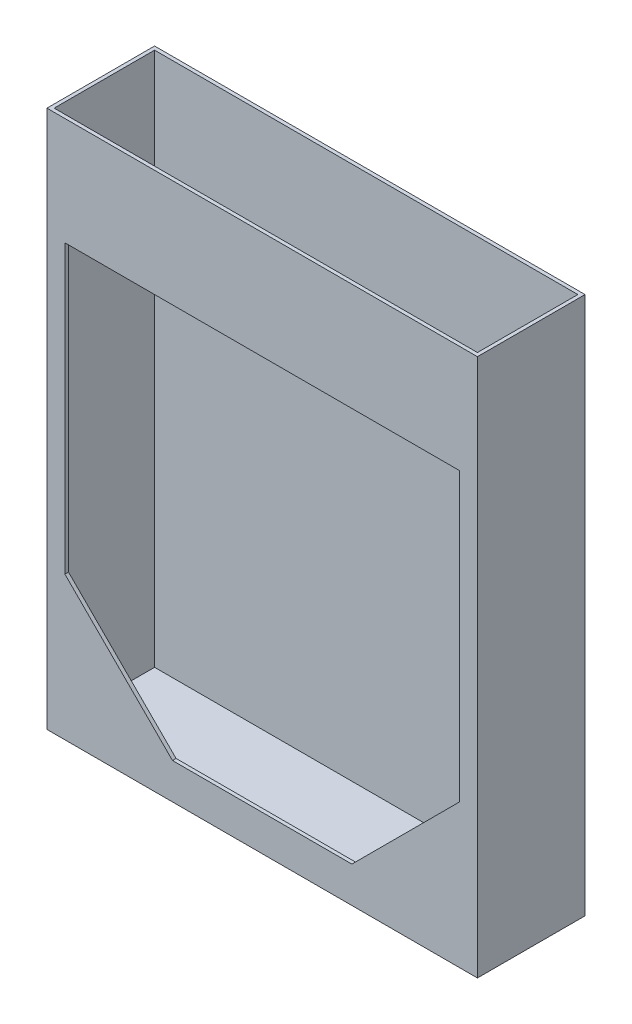
SolidWorks part; units mm, degrees
ref_plane "Front Plane" through (0, 0, 0) normal (0, 0, 1) x (1, 0, 0)
ref_plane "Top Plane" through (0, 0, 0) normal (0, 1, 0) x (1, 0, 0)
ref_plane "Right Plane" through (0, 0, 0) normal (1, 0, 0) x (0, 0, -1)
sketch "Sketch1" plane through (0, 0, 0) normal (0, 1, 0) x (1, 0, 0)
  line L0 (-152.4, 38.1) -> (152.4, -38.1) construction
  line L1 (-152.4, 38.1) -> (152.4, 38.1)
  line L2 (-152.4, 38.1) -> (-152.4, -38.1)
  line L3 (-152.4, -38.1) -> (152.4, -38.1)
  line L4 (152.4, 38.1) -> (152.4, -38.1)
  dimension "D1" = 304.8
  dimension "D2" = 76.2
extrude "Boss-Extrude1" add sketch "Sketch1" along normal mid plane 381
shell "Shell1" thickness 2.54 removed face at (0, 190.5, 0)
sketch "Sketch2" plane through (0, 0, 38.1) normal (0, 0, 1) x (1, 0, 0)
  line L0 (-152.4, 190.5) -> (-152.4, -190.5) construction
  line L1 (-139.7, 114.3) -> (139.7, 114.3)
  line L2 (-139.7, 114.3) -> (-139.7, -88.9)
  line L3 (-63.5, -165.1) -> (63.5, -165.1)
  line L4 (139.7, 114.3) -> (139.7, -88.9)
  line L5 (-139.7, 0) -> (0, 0) construction
  line L6 (0, 0) -> (139.7, 0) construction
  line L8 (-152.4, -190.5) -> (152.4, -190.5) construction
  line L9 (-139.7, -88.9) -> (-63.5, -165.1)
  line L10 (63.5, -165.1) -> (139.7, -88.9)
  line L11 (-152.4, 190.5) -> (152.4, 190.5) construction
  dimension "D1" = 12.7
  dimension "D2" = 25.4
  dimension "D3" = 45
  dimension "D4" = 76.2
  dimension "D5" = 76.2
extrude "Cut-Extrude1" cut sketch "Sketch2" against normal up to next
